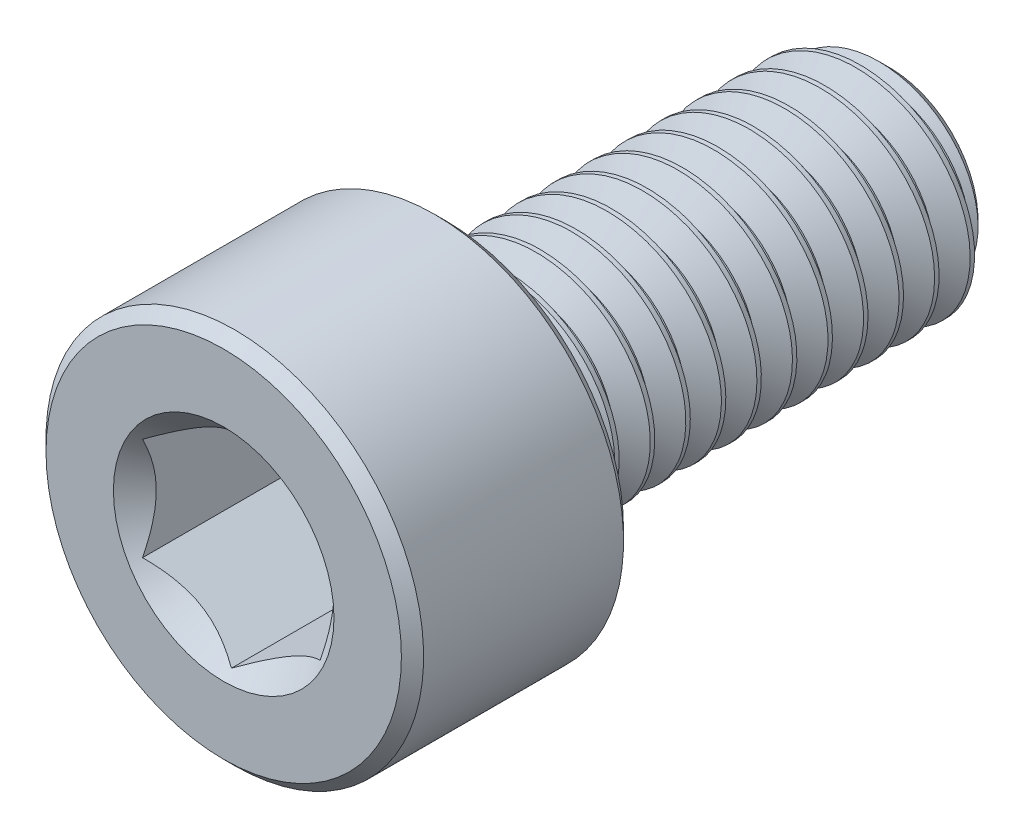
SolidWorks part; units mm, degrees
ref_plane "Front Plane" through (0, 0, 0) normal (0, 0, 1) x (1, 0, 0)
ref_plane "Top Plane" through (0, 0, 0) normal (0, 1, 0) x (1, 0, 0)
ref_plane "Right Plane" through (0, 0, 0) normal (1, 0, 0) x (0, 0, -1)
sketch "Sketch1" plane through (0, 0, 0) normal (1, 0, 0) x (0, 0, -1)
  line L0 (-7.5, 0) -> (7.5, 0) construction
  line L1 (7.5, 0) -> (7.5, 1.9804) construction
  line L2 (7.5, 1.9804) -> (6.9804, 2.5) construction
  line L3 (6.9804, 2.5) -> (6.9, 2.5) construction
  line L4 (6.9, 2.5) -> (-2.5, 2.5) construction
  line L5 (-2.5, 2.5) -> (-2.5, 4.25) construction
  line L6 (-2.5, 4.25) -> (-7.5, 4.25) construction
  line L7 (-7.5, 4.25) -> (-7.5, 0) construction
  line L8 (7.5, 1.9804) -> (7.5, 2.5) construction
  line L9 (7.45, 2.5866) -> (7.85, 1.8938) construction
  line L10 (7.85, 1.8938) -> (8.25, 2.5866) construction
  line L11 (8.25, 2.5866) -> (7.45, 2.5866) construction
  line L12 (7.85, 2.5866) -> (7.85, 2.5) construction
  line L13 (7.85, 1.8938) -> (7.85, 1.9804) construction
  line L14 (7.8, 1.9804) -> (7.9, 1.9804) construction
  line L15 (7.5, 2.5) -> (8.2, 2.5) construction
  line L16 (7.475, 2.5433) -> (8.225, 2.5433) construction
  line L17 (7.5, 0) -> (7.5, -2.5) construction
  line L18 (-2.75, 4.25) -> (-2.5, 4) construction
  line L19 (-7.25, 4.25) -> (-7.5, 4) construction
  line L20 (-2.5, 2.5) -> (-2.5, 0) construction
  line L21 (-2.5, 1.25) -> (0.8333, 1.25) construction
  line L22 (0.8333, 1.25) -> (4.1667, 1.25) construction
  line L23 (4.1667, 1.25) -> (7.5, 1.25) construction
  line L24 (0.8333, 1.25) -> (0.8333, 2.5) construction
  line L25 (0.8333, 2.5) -> (0.8333, 4.25) construction
  line L26 (4.1667, 1.25) -> (4.1667, 4.25) construction
  point P0 (-7.5, 2)
  point P3 (5.5, 2.5)
  point P4 (0, 0)
  point P18 (4.1667, 2.5)
  point P22 (7.85, 1.9804)
  point P24 (6.9, 2.5)
  point P25 (7.85, 2.5)
  point P28 (7.85, 2.5433)
  point P29 (5.5, -2.5)
  point P30 (0.8333, 2.5)
  point P31 (-5, 4.25)
  point P37 (-3.375, 4.25)
  point P38 (-7.125, 4.25)
  point P45 (0.8333, 1.25)
  point P46 (4.1667, 1.25)
  dimension "D2" = 0.1
  dimension "D7" = 0.25
  dimension "D8" = 0.25
  dimension "D9" = 0.25
  dimension "D10" = 0.125
  dimension "D11" = 0.625
  dimension "Drive Size" = 4
  dimension "Head Diameter" = 8.5
  dimension "Head Height" = 5
  dimension "Thread Pitch" = 0.8
  dimension "Thread Dia" = 5
  dimension "Length" = 10
  dimension "D12" = 0.6
  dimension "D4" = 2
  dimension "D3" = 45
sketch "Sketch2" plane through (0, 0, 0) normal (1, 0, 0) x (0, 0, -1)
  line L0 (-7.5, 0) -> (-7.5, 4)
  line L1 (-7.25, 4.25) -> (-2.75, 4.25)
  line L2 (-2.5, 4) -> (-2.5, 2.75)
  line L4 (6.9804, 2.5) -> (7.5, 1.9804)
  line L5 (7.5, 1.9804) -> (7.5, 0)
  line L6 (-2.5, 4.25) -> (-7.5, 4.25) construction
  line L7 (7.5, 0) -> (-7.5, 0)
  line L8 (-7.25, 4.25) -> (-7.5, 4) construction
  line L10 (-7.25, 4.25) -> (-7.5, 4)
  line L14 (-2.75, 4.25) -> (-2.5, 4) construction
  line L16 (-2.75, 4.25) -> (-2.5, 4)
  line L17 (-2.5, 2.5) -> (-2.5, 4.25) construction
  line L19 (-2.25, 2.5) -> (6.9804, 2.5)
  line L20 (6.9, 2.5) -> (-2.5, 2.5) construction
  arc A1 (-2.5, 2.75) -> (-2.25, 2.5) centre (-2.25, 2.75) ccw
  dimension "D3" = 0.25
revolve "Revolve1" add sketch "Sketch2" angle 360 about L7
sketch "Sketch3" plane through (0, 0, 7.5) normal (0, 0, 1) x (1, 0, 0)
  line L1 (2, -1.1547) -> (2, 1.1547)
  line L2 (2, 1.1547) -> (0, 2.3094)
  line L3 (0, 2.3094) -> (-2, 1.1547)
  line L4 (-2, 1.1547) -> (-2, -1.1547)
  line L5 (-2, -1.1547) -> (0, -2.3094)
  line L6 (0, -2.3094) -> (2, -1.1547)
  circle A0 centre (0, 0) radius 2 construction
  circle A1 centre (0, 0) radius 4.25 construction
  circle A2 centre (0, 0) radius 4.25 construction
  circle A3 centre (0, 0) radius 2.3094 construction
  point P13 (0, 0)
  dimension "D1" = 4.6188
extrude "Cut-Extrude1" cut sketch "Sketch3" against normal offset from surface (4 mm away) 1 up to face at (0, 4, 2.5)
sketch "Sketch4" plane through (0, 0, 7.5) normal (0, 0, 1) x (1, 0, 0)
  circle A0 centre (0, 0) radius 2.4826
  dimension "D1" = 4.9652
extrude "Cut-Extrude2" cut sketch "Sketch4" against normal up to vertex (2.5 mm away) draft 45 up to point (0, 4.25, 5)
sketch "Sketch11" plane through (0, 0, 0) normal (1, 0, 0) x (0, 0, -1)
  line L0 (-7.5, 0) -> (7.5, 0) construction
  line L1 (-7.5, 0) -> (7.5, 0) construction
  line L2 (-0.625, 0) -> (-0.625, 2.5) construction
  line L3 (6.9, 2.5) -> (-2.5, 2.5) construction
  line L4 (5.625, 0) -> (5.625, 2.5) construction
  line L6 (7.5, 1.9804) -> (7.5, 2.5) construction
  point P2 (-0.625, 0)
  point P3 (5.625, 0)
  dimension "D1" = 1.875
  dimension "D2" = 1.875
sketch "Sketch6" plane through (0, 0, -7.5) normal (0, 0, -1) x (-1, 0, 0)
  circle A0 centre (0, 0) radius 2.5
curve "Helix/Spiral1" pitch 0.8 height 10.8 radius 2.5 centre (0, 0, -7.5) axis (0, 0, 1) start towards (0, 1, 0)
sketch "Sketch10" plane through (0, 0, 0) normal (1, 0, 0) x (0, 0, -1)
  line L0 (-2.25, -4.25) -> (-2.25, 4.25)
  line L5 (-7.5, 0) -> (7.5, 0) construction
  line L6 (-2.25, 2.5) -> (-2.25, -2.5) construction
  point P3 (-2.25, 0)
split "Split1" trim tools "Sketch10" bodies to split 106 resulting bodies 114 115
sketch "Sketch7" plane through (0, 0, 0) normal (1, 0, 0) x (0, 0, -1)
  line L0 (7.475, 2.5433) -> (8.225, 2.5433)
  line L1 (8.225, 2.5433) -> (7.9, 1.9804)
  line L2 (7.9, 1.9804) -> (7.8, 1.9804)
  line L3 (7.8, 1.9804) -> (7.475, 2.5433)
sweep "Cut-Sweep1" cut profiles "Sketch7" path "Helix/Spiral1" align with end faces yes
sketch "Sketch8" plane through (0, 0, 0) normal (1, 0, 0) x (0, 0, -1)
  line L0 (-2.5, 0) -> (-2.5, 2.5)
  line L1 (-2.25, -2.5) -> (-2.25, 2.5) construction
  line L2 (-2.5, 2.5) -> (-2.25, 2.5)
  line L4 (-2.25, 2.5) -> (-0.8066, 0)
  line L5 (-0.8066, 0) -> (-2.5, 0)
  line L6 (6.9, 2.5) -> (-2.5, 2.5) construction
  line L7 (-7.5, 0) -> (7.5, 0) construction
  dimension "D1" = 60
revolve "Revolve2" add sketch "Sketch8" angle 360 about L5
equation "\"D2@Sketch1\" = \"Thread Pitch@Sketch1\" / 8"
equation "\"D4@Helix/Spiral1\" = \"Thread Pitch@Sketch1\""
equation "\"D7@Sketch1\" = \"Head Height@Sketch1\" * .05"
equation "\"D8@Sketch1\"=\"D7@Sketch1\""
equation "\"D9@Sketch1\"=\"D7@Sketch1\""
equation "\"D10@Sketch1\"=\"D7@Sketch1\"/2"
equation "\"D11@Sketch1\"=\"D10@Sketch1\"*5"
equation "\"D4@Sketch1\"=\"Thread Pitch@Sketch1\"*2.5"
equation "\"D12@Sketch1\"=\"Thread Pitch@Sketch1\"*.75"
equation "\"D3@Helix/Spiral1\"=\"Length@Sketch1\"+\"Thread Pitch@Sketch1\""
equation "\"D3@Sketch2\"=\"Thread Dia@Sketch1\"*0.05"
equation "\"D1@Sketch11\"=\"Length@Sketch1\"*0.1875"
equation "\"D2@Sketch11\"=\"D1@Sketch11\""
equation "\"D1@Sketch4\"=\"D1@Sketch3\"*1.075"
